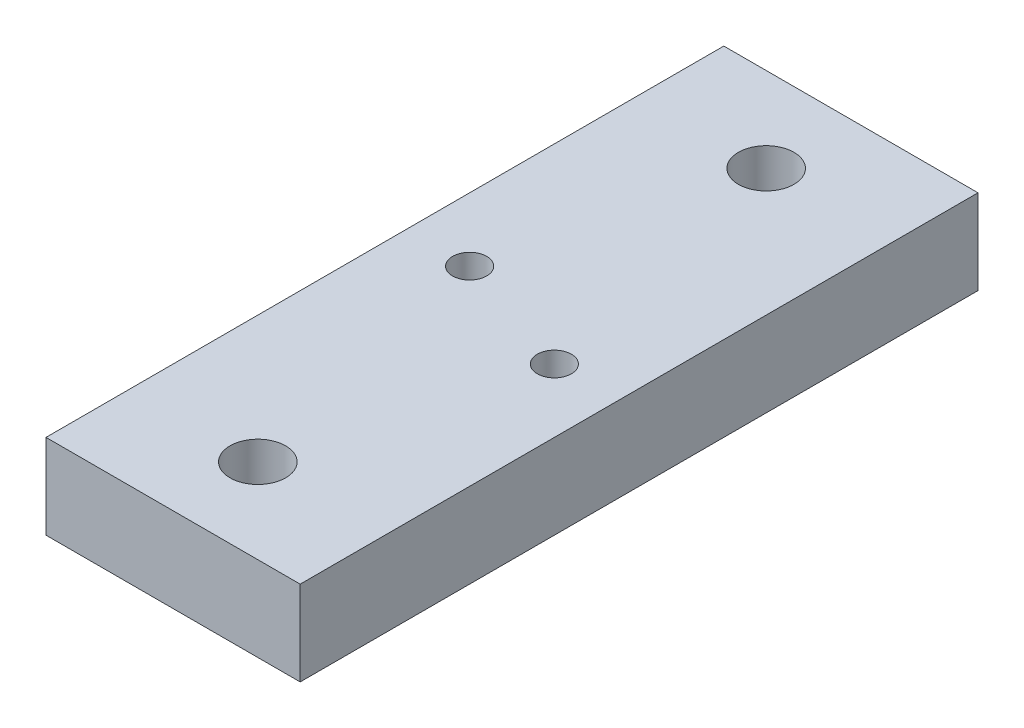
SolidWorks part; units mm, degrees
material "6061-T6 (SS)"
ref_plane "Front Plane" through (0, 0, 0) normal (0, 0, 1) x (1, 0, 0)
ref_plane "Top Plane" through (0, 0, 0) normal (0, 1, 0) x (1, 0, 0)
ref_plane "Right Plane" through (0, 0, 0) normal (1, 0, 0) x (0, 0, -1)
sketch "Sketch1" plane through (0, 0, 0) normal (0, 1, 0) x (1, 0, 0)
  line L1 (0, 0) -> (38.1, 0)
  line L2 (0, 0) -> (0, 101.6)
  line L3 (0, 101.6) -> (38.1, 101.6)
  line L4 (38.1, 0) -> (38.1, 101.6)
  circle A0 centre (19.05, 88.9) radius 4.1656
  circle A1 centre (19.05, 12.7) radius 4.1656
  dimension "D3" = 8.3312
  dimension "D4" = 8.3312
  dimension "D1" = 38.1
  dimension "D2" = 101.6
  dimension "D5" = 19.05
  dimension "D6" = 12.7
  dimension "D7" = 19.05
  dimension "D8" = 12.7
extrude "Boss-Extrude1" add sketch "Sketch1" along normal blind 12.7
hole_wizard "CBORE for #10 Hex Machine Screw1" positions "Sketch2" profile "Sketch3" counterbore size "#10" standard "ANSI Inch" end condition through all
sketch "Sketch2" plane through (0, 0, 0) normal (0, -1, 0) x (-1, 0, 0)
  line L0 (0, 101.6) -> (0, 0) construction
  point P0 (-28.575, 47.625)
  point P2 (-9.525, 53.975)
  dimension "D1" = 9.525
  dimension "D2" = 47.625
  dimension "D3" = 9.525
  dimension "D4" = 47.625
sketch "Sketch3" plane through (28.575, 0, -47.625) normal (1, 0, 0) x (0, 0, -1)
  line L0 (0, 0) -> (0, 12.7)
  line L1 (0, 12.7) -> (2.5527, 12.7)
  line L3 (2.5527, 12.7) -> (2.5527, 3.048)
  line L4 (2.5527, 3.048) -> (7.1437, 3.048)
  line L5 (7.1437, 3.048) -> (7.1438, 0)
  line L7 (7.1438, 0) -> (0, 0)
  line L11 (0, -6.35) -> (0, 107.95) construction
  dimension "Thru Hole Dia." = 5.1054
  dimension "Thru Hole Depth" = 12.7
  dimension "C'Bore Dia." = 14.2875
  dimension "C'Bore Depth" = 3.048
